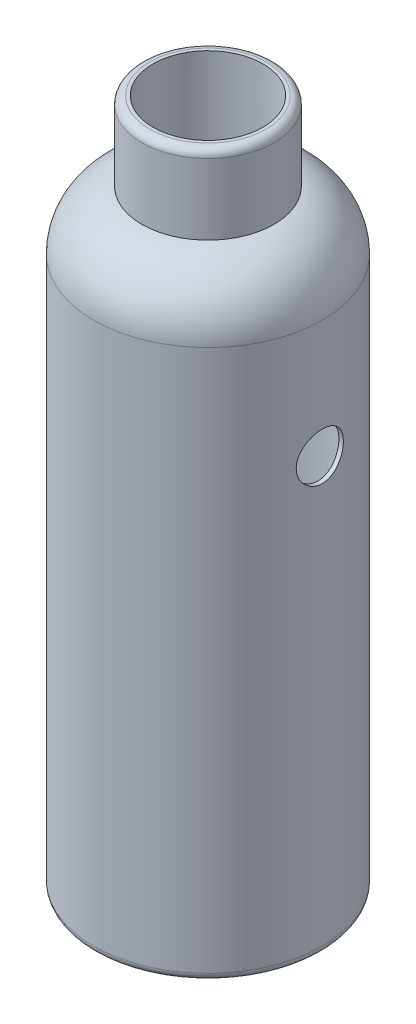
SolidWorks part; units mm, degrees
ref_plane "Front Plane" through (0, 0, 0) normal (0, 0, 1) x (1, 0, 0)
ref_plane "Top Plane" through (0, 0, 0) normal (0, 1, 0) x (1, 0, 0)
ref_plane "Right Plane" through (0, 0, 0) normal (1, 0, 0) x (0, 0, -1)
sketch "Sketch1" plane through (0, 0, 0) normal (0, 1, 0) x (1, 0, 0)
  circle A0 centre (0, 0) radius 36.9633
  dimension "D1" = 73.9267
extrude "Boss-Extrude1" add sketch "Sketch1" along normal blind 171.45
fillet "Fillet1" radius 2.54 1 edges at (0, 0, 36.9633)
ref_plane "Plane1" through (0, 196.85, 0) normal (0, 1, 0) x (1, 0, 0)
sketch "Sketch2" plane through (0, 196.85, 0) normal (0, 1, 0) x (1, 0, 0)
  circle A0 centre (0, 0) radius 20.6883
  dimension "D1" = 41.3766
sketch "Sketch10" plane through (0, 171.45, 0) normal (0, 1, 0) x (1, 0, 0)
  circle A0 centre (0, 0) radius 36.9633
  dimension "D1" = 73.9267
extrude "Boss-Extrude2" add sketch "Sketch10" along normal blind 25.4
fillet "Fillet2" radius 19.05 1 edges at (0, 196.85, 36.9633)
sketch "Sketch11" plane through (0, 196.85, 0) normal (0, 1, 0) x (1, 0, 0)
  circle A0 centre (0, 0) radius 21.3678
  dimension "D1" = 42.7355
extrude "Boss-Extrude3" add sketch "Sketch11" along normal blind 25.4
fillet "Fillet3" radius 2.54 1 edges at (0, 222.25, 21.3678)
sketch "Sketch12" plane through (0, 222.25, 0) normal (0, 1, 0) x (1, 0, 0)
  circle A0 centre (0, 0) radius 17.78
  dimension "D1" = 35.56
extrude "Cut-Extrude1" cut sketch "Sketch12" against normal blind 221.742
sketch "Sketch13" plane through (0, 0.508, 0) normal (0, 1, 0) x (1, 0, 0)
  circle A0 centre (0, 0) radius 35.56
  dimension "D1" = 71.12
extrude "Cut-Extrude2" cut sketch "Sketch13" along normal blind 171.45
sketch "Sketch14" plane through (0, 0, 0) normal (0, 0, 1) x (1, 0, 0)
  line L5 (35.56, 171.958) -> (0, 171.958)
  line L6 (-35.56, 171.958) -> (35.56, 171.958) construction
  line L7 (0, 171.958) -> (0, 196.85)
  line L8 (20.6883, 196.85) -> (-20.6883, 196.85) construction
  line L9 (35.56, 171.958) -> (35.56, 177.8)
  line L10 (16.51, 196.85) -> (0, 196.85)
  arc A1 (35.56, 177.8) -> (16.51, 196.85) centre (16.51, 177.8) ccw
  dimension "D1" = 19.05
revolve "Cut-Revolve1" cut sketch "Sketch14" angle 360 about L7
sketch "Sketch15" plane through (0, 0, 0) normal (1, 0, 0) x (0, 0, -1)
  line L0 (36.9634, 177.8) -> (-36.9634, 177.8) construction
  line L1 (0, 177.8) -> (0, 85.8043) construction
  circle A0 centre (0, 139.7) radius 7.62
  point P9 (0, 157.469)
  dimension "D1" = 15.24
  dimension "D2" = 38.1
extrude "Cut-Extrude3" cut sketch "Sketch15" against normal blind 2.54 and the other way through all
